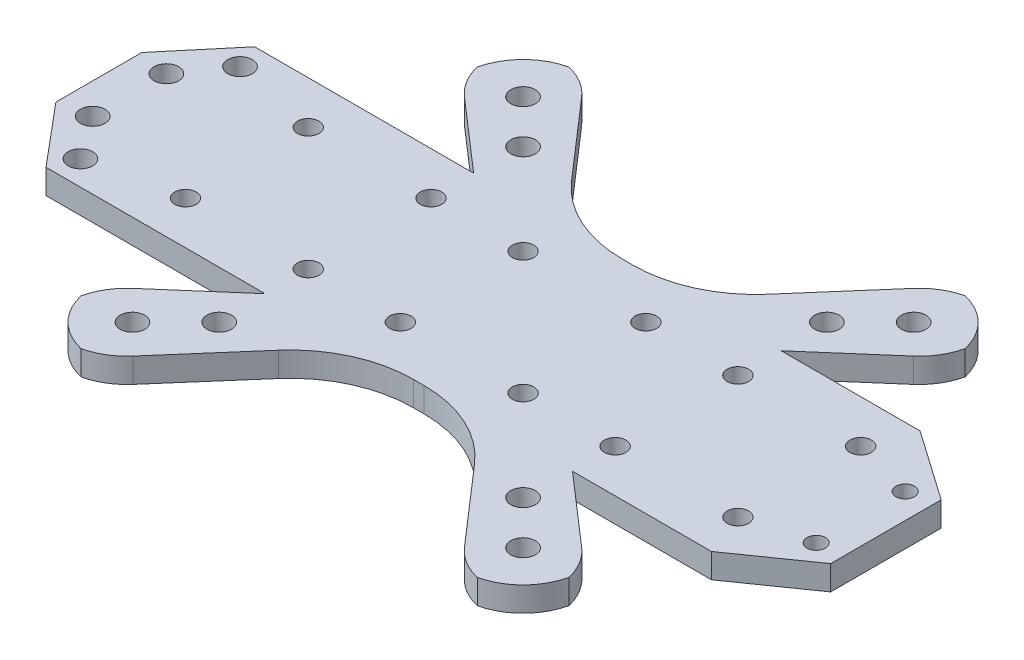
SolidWorks part; units mm, degrees
ref_plane "Front Plane" through (0, 0, 0) normal (0, 0, 1) x (1, 0, 0)
ref_plane "Top Plane" through (0, 0, 0) normal (0, 1, 0) x (1, 0, 0)
ref_plane "Right Plane" through (0, 0, 0) normal (1, 0, 0) x (0, 0, -1)
sketch "Sketch1" plane through (0, 0, 0) normal (0, 1, 0) x (1, 0, 0)
  line L1 (-15, -16) -> (15, -16) construction
  line L2 (-15, -16) -> (-15, 16) construction
  line L3 (-15, 16) -> (15, 16) construction
  line L4 (15, -16) -> (15, 16) construction
  line L5 (-15, -16) -> (15, 16) construction
  line L6 (-15, 16) -> (15, -16) construction
  line L7 (40, -40) -> (-40, -40)
  line L8 (40, -40) -> (40, 40)
  line L9 (40, 40) -> (-40, 40)
  line L10 (-40, -40) -> (-40, 40)
  line L11 (40, -40) -> (-40, 40) construction
  line L12 (40, 40) -> (-40, -40) construction
  line L13 (10, -10) -> (-10, -10) construction
  line L14 (10, -10) -> (10, 10) construction
  line L15 (10, 10) -> (-10, 10) construction
  line L16 (-10, -10) -> (-10, 10) construction
  line L17 (10, -10) -> (-10, 10) construction
  line L18 (10, 10) -> (-10, -10) construction
  circle A0 centre (-24.7487, 24.7487) radius 2
  circle A1 centre (24.7487, 24.7487) radius 2
  circle A2 centre (24.7487, -24.7487) radius 2
  circle A3 centre (-24.7487, -24.7487) radius 2
  circle A4 centre (-10, 10) radius 1.75
  circle A5 centre (10, 10) radius 1.75
  circle A6 centre (10, -10) radius 1.75
  circle A7 centre (-10, -10) radius 1.75
  circle A8 centre (31.8198, 31.8198) radius 2
  circle A9 centre (-31.8198, 31.8198) radius 2
  circle A10 centre (-31.8198, -31.8198) radius 2
  circle A11 centre (31.8198, -31.8198) radius 2
  point P0 (0, 0)
  point P6 (0, 0)
  point P19 (0, 0)
  dimension "D5" = 35
  dimension "D11" = 45
  dimension "D1" = 30
  dimension "D2" = 32
  dimension "D3" = 80
  dimension "D4" = 80
  dimension "D6" = 35
  dimension "D7" = 35
  dimension "D8" = 35
  dimension "D9" = 20
  dimension "D10" = 20
  dimension "D12" = 45
  dimension "D13" = 45
  dimension "D14" = 45
extrude "Boss-Extrude1" add sketch "Sketch1" along normal blind 4
sketch "Sketch2" plane through (0, 4, 0) normal (0, 1, 0) x (1, 0, 0)
  line L0 (-40, 30) -> (-40, -30)
  line L1 (15, -15) -> (-15, -15) construction
  line L2 (15, -15) -> (15, 15) construction
  line L3 (15, 15) -> (-15, 15) construction
  line L4 (-15, -15) -> (-15, 15) construction
  line L5 (15, -15) -> (-15, 15) construction
  line L6 (15, 15) -> (-15, -15) construction
  line L11 (-40, -30) -> (-17, -10)
  line L12 (-40, 40) -> (-40, -40) construction
  line L13 (-17, -10) -> (-17, 10)
  line L14 (-17, 10) -> (-40, 30)
  line L15 (40, 40) -> (-40, 40) construction
  line L16 (-40, -40) -> (40, -40) construction
  line L17 (30, 40) -> (-30, 40)
  line L18 (10, 17) -> (30, 40)
  line L19 (-10, 17) -> (10, 17)
  line L20 (-30, 40) -> (-10, 17)
  line L21 (40, -30) -> (40, 30)
  line L22 (17, -10) -> (40, -30)
  line L23 (17, 10) -> (17, -10)
  line L24 (40, 30) -> (17, 10)
  line L25 (-30, -40) -> (30, -40)
  line L26 (-10, -17) -> (-30, -40)
  line L27 (10, -17) -> (-10, -17)
  line L28 (30, -40) -> (10, -17)
  point P0 (0, 0)
  point P6 (-40, 0)
  point P32 (0, 0)
  dimension "D1" = 30
  dimension "D2" = 30
  dimension "D3" = 10
  dimension "D4" = 30
  dimension "D5" = 10
  dimension "D6" = 30
  dimension "D8" = 23
  dimension "D7" = 4
extrude "Cut-Extrude2" cut sketch "Sketch2" against normal through all
fillet "Fillet1" radius 10 12 edges at (-30, 2, 40) (-40, 2, 40) (-40, 2, 30) (-40, 2, -40) (-40, 2, -30) (-30, 2, -40) (30, 2, -40) (40, 2, -40) (40, 2, -30) (40, 2, 30) (40, 2, 40) (30, 2, 40)
fillet "Fillet2" radius 20 8 edges at (-17, 2, 10) (-17, 2, -10) (-10, 2, -17) (10, 2, -17) (17, 2, -10) (17, 2, 10) (10, 2, 17) (-10, 2, 17)
sketch "Sketch5" plane through (0, 4, 0) normal (0, 1, 0) x (1, 0, 0)
  line L0 (-0.8874, 17) -> (13.289, 12.1235)
  line L1 (-0.8874, 17) -> (59.1126, 17)
  line L2 (-0.8874, 17) -> (-0.8874, -17) construction
  line L3 (-0.8874, -17) -> (59.1126, -17)
  line L4 (59.1126, 17) -> (59.1126, -17)
  line L5 (13.289, 12.1235) -> (13.289, -13.4962)
  line L6 (13.289, -13.4962) -> (-0.8874, -17)
  dimension "D1" = 34
  dimension "D2" = 60
extrude "Boss-Extrude3" add sketch "Sketch5" against normal blind 4
sketch "Sketch6" plane through (0, 4, 0) normal (0, 1, 0) x (1, 0, 0)
  line L0 (10, 10) -> (35.6615, 10) construction
  line L2 (25, 10) -> (45, 10) construction
  line L3 (25, 10) -> (25, -10) construction
  line L4 (25, -10) -> (45, -10) construction
  line L5 (45, 10) -> (45, -10) construction
  circle A2 centre (25, 10) radius 1.75
  circle A4 centre (45, 10) radius 1.75
  circle A5 centre (25, -10) radius 1.75
  circle A6 centre (45, -10) radius 1.75
  dimension "D1" = 15
  dimension "D2" = 20
  dimension "D3" = 20
extrude "Cut-Extrude3" cut sketch "Sketch6" against normal blind 4
mirror "Mirror1" about plane through (0, 0, 0) normal (1, 0, 0) of "Cut-Extrude3", "Boss-Extrude3"
sketch "Sketch7" plane through (0, 4, 0) normal (0, 1, 0) x (1, 0, 0)
  line L0 (55, 17) -> (55, -17) construction
  line L1 (59.1126, 17) -> (25.05, 17) construction
  line L2 (25.05, -17) -> (59.1126, -17) construction
  circle A4 centre (55, 7.25) radius 1.5
  circle A5 centre (55, -7.25) radius 1.5
  circle A6 centre (45, 10) radius 1.75 construction
  dimension "D1" = 14.5
  dimension "D2" = 10
  dimension "D3" = 9.75
extrude "Cut-Extrude4" cut sketch "Sketch7" against normal blind 10
chamfer "Chamfer1" distance 8 angle 55 2 edges at (59.1126, 2, 17) (59.1126, 2, -17) first distance on face at (59.1126, 2, 0)
sketch "Sketch8" plane through (0, 4, 0) normal (0, 1, 0) x (1, 0, 0)
  line L1 (-59.1126, 17) -> (-69.1126, 17)
  line L2 (-59.1126, 17) -> (-59.1126, -17)
  line L3 (-59.1126, -17) -> (-69.1126, -17)
  line L4 (-69.1126, 17) -> (-69.1126, -17)
  dimension "D1" = 10
  dimension "D2" = 34
extrude "Boss-Extrude4" add sketch "Sketch8" against normal blind 4
sketch "Sketch9" plane through (0, 4, 0) normal (0, 1, 0) x (1, 0, 0)
  line L0 (-69.1126, 0) -> (-63.0766, 0) construction
  line L1 (-69.1126, 17) -> (-69.1126, -17) construction
  line L2 (-25.05, -17) -> (-69.1126, -17) construction
  line L3 (-69.1126, 17) -> (-25.05, 17) construction
  circle A0 centre (-64.1126, 6) radius 2
  circle A1 centre (-64.1126, -6) radius 2
  circle A2 centre (-59.1126, -13) radius 2
  circle A3 centre (-59.1126, 13) radius 2
  dimension "D1" = 6
  dimension "D5" = 4
  dimension "D7" = 4
  dimension "D2" = 6
  dimension "D3" = 5
  dimension "D4" = 5
  dimension "D6" = 10
  dimension "D8" = 10
extrude "Cut-Extrude5" cut sketch "Sketch9" against normal blind 4
chamfer "Chamfer2" distance 10 angle 40 2 edges at (-69.1126, 2, -17) (-69.1126, 2, 17) first distance on face at (-69.1126, 2, 0)
